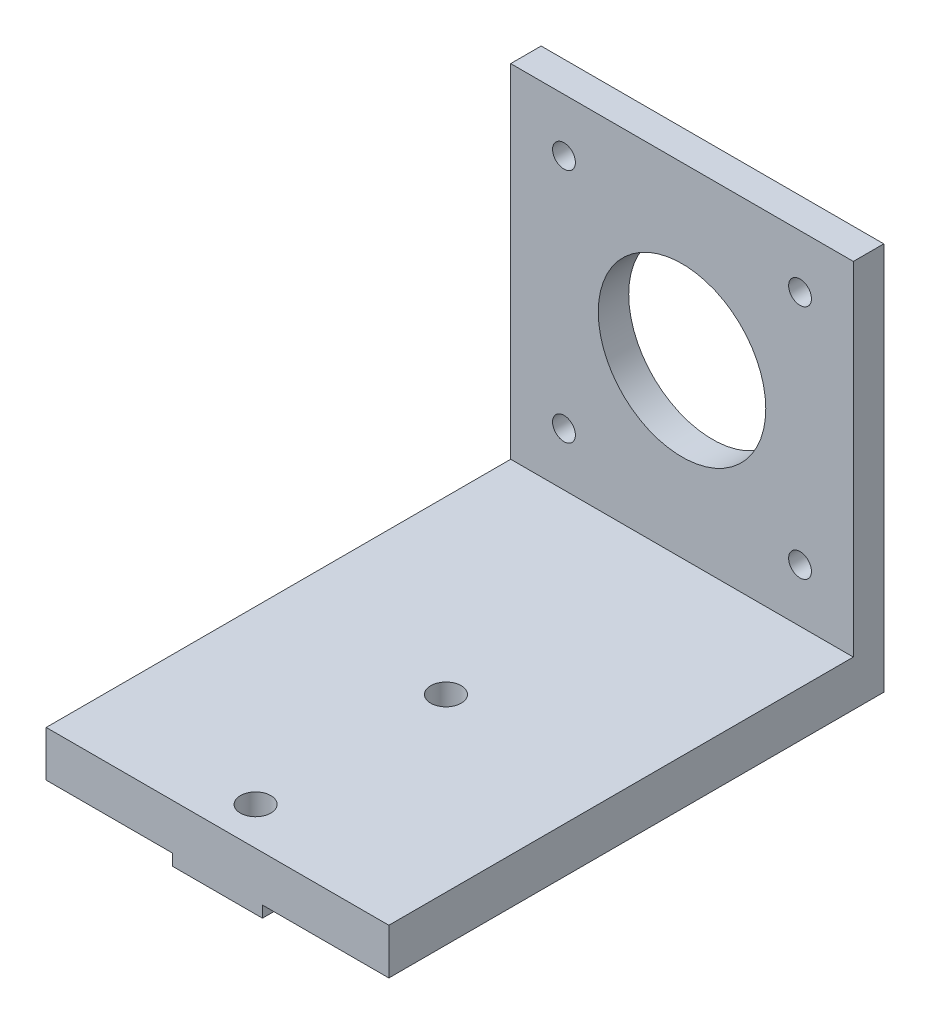
SolidWorks part; units mm, degrees
ref_plane "Front Plane" through (0, 0, 0) normal (0, 0, 1) x (1, 0, 0)
ref_plane "Top Plane" through (0, 0, 0) normal (0, 1, 0) x (1, 0, 0)
ref_plane "Right Plane" through (0, 0, 0) normal (1, 0, 0) x (0, 0, -1)
sketch "Sketch1" plane through (0, 0, 0) normal (0, 0, 1) x (1, 0, 0)
  line L0 (16.7358, 20.15) -> (-16.7358, 20.15)
  line L1 (-16.7358, 20.15) -> (-20.15, 16.7358)
  line L2 (-20.15, 16.0771) -> (-20.15, -16.7358)
  line L5 (-16.7358, -20.15) -> (16.7358, -20.15)
  line L7 (20.15, -16.7358) -> (20.15, 16.7358)
  line L8 (20.15, 16.7358) -> (16.7358, 20.15)
  line L9 (-20.15, 16.0771) -> (-20.15, 16.7358)
  line L10 (-20.15, -16.7358) -> (-20.15, -20.15)
  line L11 (-20.15, -20.15) -> (-16.7358, -20.15)
  line L12 (16.7358, -20.15) -> (20.15, -20.15)
  line L13 (20.15, -20.15) -> (20.15, -16.7358)
  line L15 (-22.5, 22.5) -> (22.5, 22.5)
  line L16 (-22.5, 22.5) -> (-22.5, -22.5)
  line L17 (-22.5, -22.5) -> (22.5, -22.5)
  line L18 (22.5, 22.5) -> (22.5, -22.5)
  circle A0 centre (-15.5, 15.5) radius 1.5
  circle A1 centre (-15.5, -15.5) radius 1.5
  circle A2 centre (15.5, 15.5) radius 1.5
  circle A3 centre (15.5, -15.5) radius 1.5
  circle A4 centre (0, 0) radius 11
  point P42 (-1.572, -13.5641)
  dimension "D1" = 22
  dimension "D2" = 3
  dimension "D3" = 3
  dimension "D4" = 3
  dimension "D5" = 3
  dimension "D6" = 45
  dimension "D7" = 45
  dimension "D8" = 22.5
  dimension "D9" = 22.5
extrude "Boss-Extrude1" add sketch "Sketch1" along normal blind 4 contours L18 L15 L16 L17 L13 L12 L5 L11 L10 L2 L9 L1 L0 L8 L7 | L12 L13 L7 L8 L0 L1 L9 L2 L10 L11 L5 A4 A3 A2 A1 A0 region at (18.0399, 18.0399, 0) region at (0, 21.8636, 0)
sketch "Sketch2" plane through (0, -24.1499, 0) normal (0, 1, 0) x (1, 0, 0)
  line L7 (6.0001, 199.3766) -> (6.0001, -250.6234) construction
  line L8 (5.9984, 199.3766) -> (5.9984, -250.6234) construction
  line L9 (-5.9999, 199.3766) -> (-5.9999, -250.6234) construction
  line L10 (-22.5, -4) -> (-22.5, 0) construction
  line L11 (5.9001, -65) -> (-5.8999, -65)
  line L12 (5.9001, -65) -> (5.9001, 0)
  line L13 (5.9001, 0) -> (-5.8999, 0)
  line L14 (-5.8999, -65) -> (-5.8999, 0)
  line L15 (-22.5, 0) -> (22.5, 0)
  line L16 (-22.5, 0) -> (-22.5, -65)
  line L19 (-19.4999, 0) -> (19.5, 0)
  line L21 (-22.5, -65) -> (22.5, -65)
  line L22 (22.5, 0) -> (22.5, -65)
  line L25 (-22.5, -4) -> (22.5, -4) construction
  line L26 (22.5, -4) -> (22.5, 0) construction
  circle A0 centre (0.0001, -35) radius 2
  circle A1 centre (-0.0016, -60) radius 2
  point P2 (22.5, -2)
  line M5 (19.5, -250.6234) -> (19.5, 199.3766)
  line M7 (6.3, 199.3766) -> (6.3, -250.6234)
  dimension "D3" = 4
  dimension "D4" = 4
  dimension "D2" = 35
  dimension "D5" = 25
  dimension "D6" = 0
  dimension "D7" = 6
  dimension "D8" = 6
  dimension "D9" = 0.1
  dimension "D10" = 65
  dimension "D11" = 0.1
  dimension "D12" = 0
  dimension "D13" = 0
  dimension "D14" = 4
  dimension "D15" = 0
extrude "Boss-Extrude2" add sketch "Sketch2" against normal blind 6 from surface contours L22 L15 L21 M5 | L21 L15 M7 M5 | L16 L21 L14 L15 | L12 L21 L15 M7 | L14 L11 L12 L13 A1 A0 region at (0.0001, -24.1499, 31.9918) region at (6.1001, -24.1499, 32.5) region at (-14.2, -24.1499, 32.5) region at (12.9, -24.1499, 32.5) region at (21, -24.1499, 32.5) starting at face at (0, -22.5, 2)
extrude "Boss-Extrude4" add sketch "Sketch2<5>" against normal blind 1.5 from surface contours L14 L12 A1 A0 region at (0.0001, -24.1499, 31.9918) starting at face at (0.0001, -28.5, 37)
sketch "Sketch2<5>" plane through (0, -24.1499, 0) normal (0, 1, 0) x (1, 0, 0) same geometry as "Sketch2"
